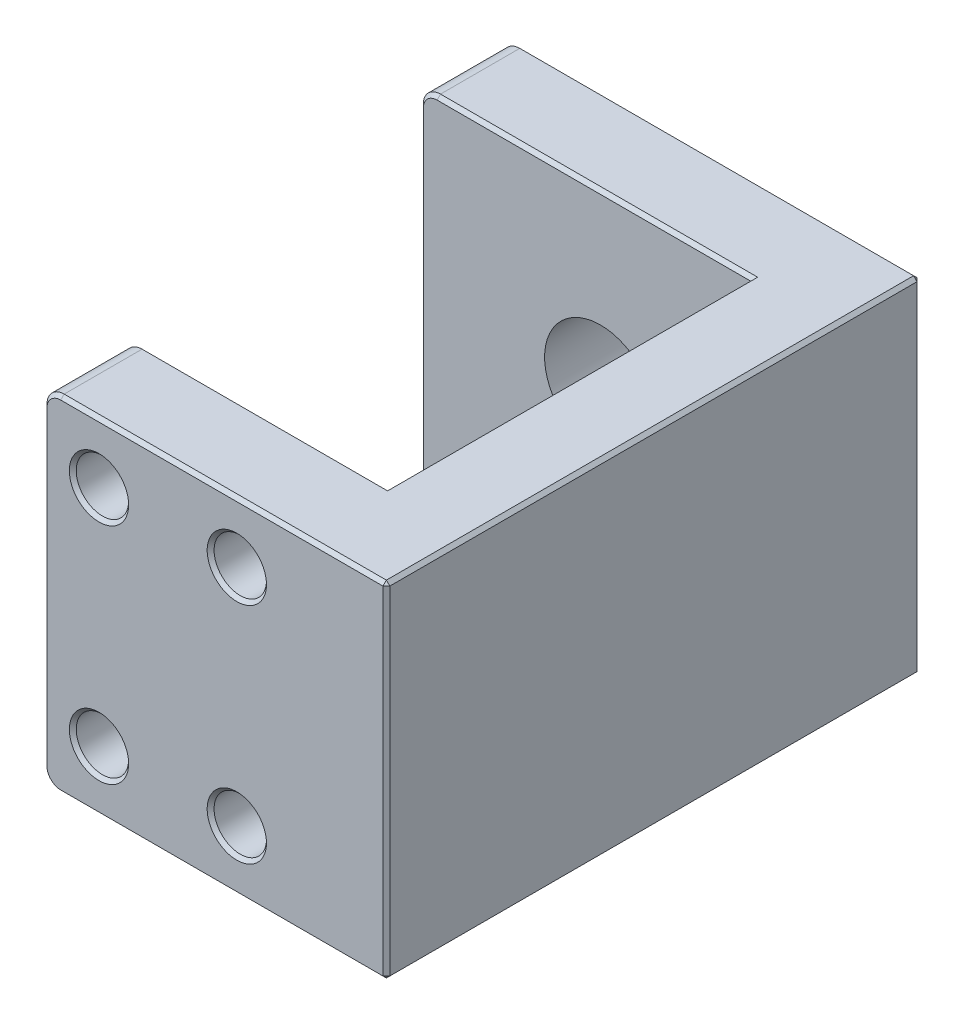
SolidWorks part; units mm, degrees
other "标注1"
sketch "草图9" plane through (-10.48, 10, -1.55) normal (-0.4516, 0.1897, -0.8718) x (-0.888, 0, 0.4599)
material "6061-T6 (SS)"
ref_plane "前视基准面" through (0, 0, 0) normal (0, 0, 1) x (1, 0, 0)
ref_plane "上视基准面" through (0, 0, 0) normal (0, 1, 0) x (1, 0, 0)
ref_plane "右视基准面" through (0, 0, 0) normal (1, 0, 0) x (0, 0, -1)
sketch "草图1" plane through (0, 0, 0) normal (0, 0, 1) x (1, 0, 0)
  line L1 (13.5775, 0) -> (13.5775, 10)
  line L2 (13.5775, 0) -> (13.5775, -10)
  line L4 (-10.48, 0) -> (-10.48, 10)
  line L5 (-10.48, 10) -> (13.5775, 10)
  line L6 (13.5775, -10) -> (-10.48, -10)
  line L7 (-10.48, -10) -> (-10.48, 0)
  circle A0 centre (0, 0) radius 3.2375
extrude "凸台-拉伸1" add sketch "草图1" along normal blind 5
sketch "草图2" plane through (0, 0, 0) normal (0, 0, 1) x (1, 0, 0)
  circle A0 centre (0, 5.6) radius 1.015
  circle A1 centre (0, -5.6) radius 1.015
extrude "切除-拉伸1" cut sketch "草图2" along normal blind 2.85
chamfer "倒角1" distance 0.2 angle 45 2 edges at (1.015, -5.6, 0) (1.015, 5.6, 0)
sketch "草图5" plane through (0, 0, 0) normal (0, 0, 1) x (1, 0, 0)
  line L0 (-9, 7.275) -> (-10.48, 7.275)
  line L2 (-9, 0) -> (-9, 7.275)
  line L3 (-9, 0) -> (-9, -7.275)
  line L4 (-10.48, 10) -> (-10.48, -10) construction
  line L5 (-10.48, 7.275) -> (-10.48, -7.275)
  line L6 (-10.48, -7.275) -> (-9, -7.275)
extrude "凸台-拉伸2" add sketch "草图5" against normal blind 1.55 from surface starting at face at (-1.215, -5.6, 0)
chamfer "倒角2" distance 0.2 angle 45 4 edges at (-9.74, -7.275, -1.55) (-9, 0, -1.55) (-10.48, 0, -1.55) (-9.74, 7.275, -1.55)
fillet "圆角1" radius 0.15 4 edges at (-10.48, -7.275, -0.675) (-9, -7.275, -0.675) (-9, 7.275, -0.675) (-10.48, 7.275, -0.675)
sketch "草图6" plane through (0, 0, 0) normal (0, 0, 1) x (1, 0, 0)
  line L0 (13.5775, 10) -> (8.7275, 10)
  line L1 (13.5775, 10) -> (-10.48, 10) construction
  line L2 (8.7275, 10) -> (8.7275, -10)
  line L3 (-10.48, -10) -> (13.5775, -10) construction
  line L4 (8.7275, -10) -> (13.5775, -10)
  line L5 (13.5775, -10) -> (13.5775, 10)
extrude "凸台-拉伸3" add sketch "草图6" along normal blind 31
sketch "草图7" plane through (0, 0, 0) normal (0, 0, 1) x (1, 0, 0)
  line L0 (13.5775, 10) -> (-6.3225, 10)
  line L1 (8.7275, 10) -> (-10.48, 10) construction
  line L2 (-6.3225, 10) -> (-6.3225, -10)
  line L3 (-10.48, -10) -> (8.7275, -10) construction
  line L4 (-6.3225, -10) -> (13.5775, -10)
  line L5 (13.5775, -10) -> (13.5775, 10)
extrude "凸台-拉伸4" add sketch "草图7" against normal blind 4.92 from surface starting at face at (11.1525, 0, 31)
sketch "草图8" plane through (0, 0, 0) normal (0, 0, 1) x (1, 0, 0)
  circle A4 centre (-3.1025, 6.5) radius 1.52
  circle A5 centre (4.8975, 6.5) radius 1.52
  circle A6 centre (4.8975, -6.5) radius 1.52
  circle A7 centre (-3.1025, -6.5) radius 1.52
extrude "切除-拉伸2" cut sketch "草图8" against normal up to surface (-26.08 mm away) from surface up to face at (1.2025, 0, 26.08) starting at face at (3.6275, 0, 31)
chamfer "倒角3" distance 0.2 angle 45 4 edges at (-1.5825, -6.5, 31) (6.4175, -6.5, 31) (6.4175, 6.5, 31) (-1.5825, 6.5, 31)
fillet "圆角2" radius 1 4 edges at (-6.3225, -10, 28.54) (-10.48, -10, 2.5) (-10.48, 10, 2.5) (-6.3225, 10, 28.54)
chamfer "倒角4" distance 0.2 angle 45 27 edges at (8.7275, -10, 15.54) (1.7025, -10, 26.08) (-0.3763, -10, 5) (-6.0296, -9.7071, 26.08) (-10.1871, -9.7071, 5) (-6.3225, 0, 26.08) (-10.48, 0, 5) (-6.0296, 9.7071, 26.08) (-10.1871, 9.7071, 5) (1.7025, 10, 26.08) (-0.3763, 10, 5) (8.7275, 10, 15.54) (4.1275, -10, 31) (-6.0296, -9.7071, 31) (-10.48, -8.0625, 0) (-6.3225, 0, 31) (-10.48, 8.0625, 0) (-10.1871, -9.7071, 0) (-6.0296, 9.7071, 31) (-10.1871, 9.7071, 0) (2.0488, -10, 0) (13.5775, -10, 15.5) (4.1275, 10, 31) (2.0488, 10, 0) (13.5775, 0, 0) (13.5775, 10, 15.5) (13.5775, 0, 31)
